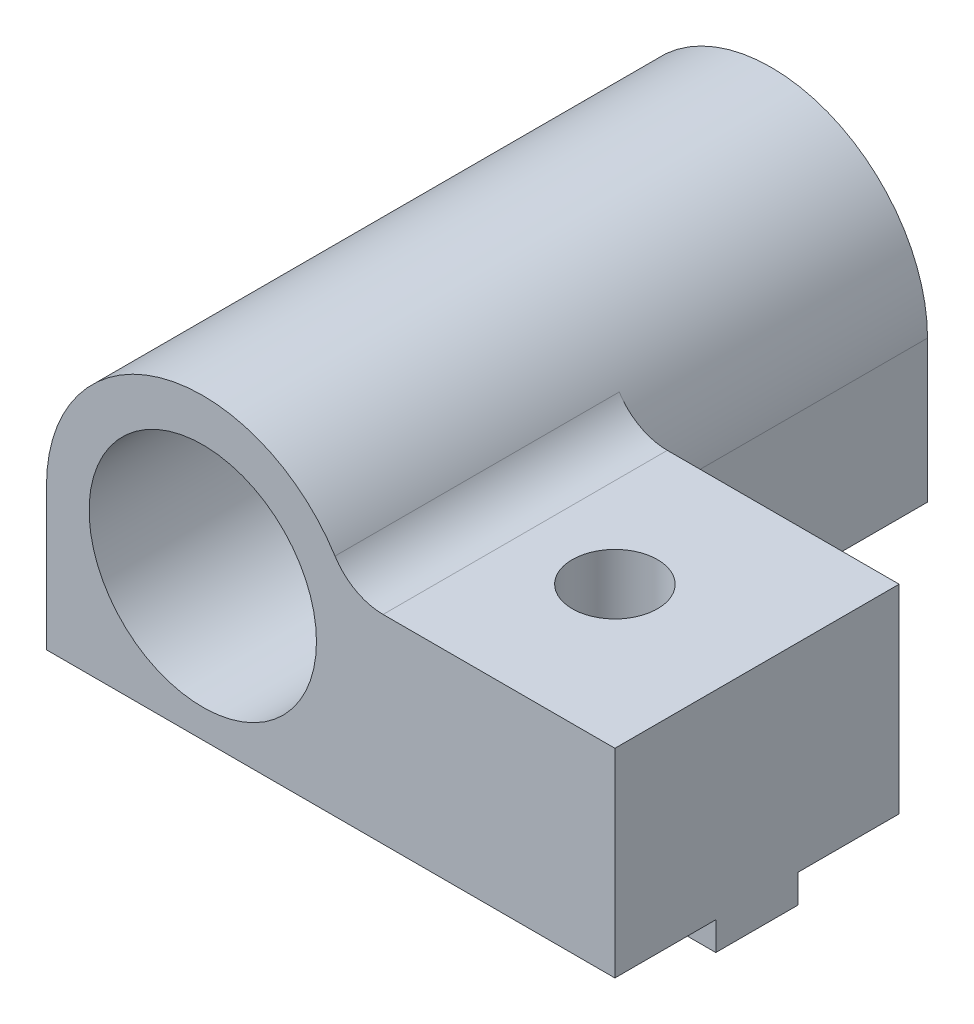
SolidWorks part; units mm, degrees
ref_plane "Front Plane" through (0, 0, 0) normal (0, 0, 1) x (1, 0, 0)
ref_plane "Top Plane" through (0, 0, 0) normal (0, 1, 0) x (1, 0, 0)
ref_plane "Right Plane" through (0, 0, 0) normal (1, 0, 0) x (0, 0, -1)
sketch "Sketch1" plane through (0, 0, 0) normal (0, 0, 1) x (1, 0, 0)
  line L0 (-5.5, 0) -> (-5.5, -5)
  line L1 (14.5, -5) -> (14.5, 2)
  line L3 (-5.5, -5) -> (14.5, -5)
  line L4 (14.5, 2) -> (5.1235, 2)
  arc A0 (-5.5, 0) -> (5.1235, 2) centre (0, 0) cw
  circle A1 centre (0, 0) radius 4
  dimension "D1" = 8
  dimension "D2" = 5.5
  dimension "D3" = 5
  dimension "D4" = 7
  dimension "D5" = 20
  dimension "D6" = 9.3765
extrude "Main" add sketch "Sketch1" along normal blind 10
sketch "Sketch3" plane through (0, -5, 0) normal (0, -1, 0) x (-1, 0, 0)
  line L0 (5.5, -10) -> (5.5, 0) construction
  line L1 (5.5, -6.45) -> (-14.5, -6.45)
  line L2 (5.5, -6.45) -> (5.5, -3.55)
  line L3 (5.5, -3.55) -> (-14.5, -3.55)
  line L4 (-14.5, -6.45) -> (-14.5, -3.55)
  line L5 (-14.5, -10) -> (-14.5, 0) construction
  line L6 (5.5, 0) -> (-14.5, 0) construction
  dimension "D1" = 2.9
  dimension "D2" = 3.55
extrude "MakerBeamRectangularGuide" add sketch "Sketch3" along normal blind 1
sketch "Sketch4" plane through (0, 2, 0) normal (0, 1, 0) x (1, 0, 0)
  line L0 (14.5, -10) -> (5.1235, -10) construction
  line L1 (14.5, -10) -> (14.5, 0) construction
  circle A0 centre (9.5, -5) radius 1.5
  dimension "D1" = 3
  dimension "D2" = 5
  dimension "D3" = 5
extrude "MakerBeamFixHole" cut sketch "Sketch4" against normal through all
fillet "Fillet1" radius 2 1 edges at (5.1235, 2, 5)
sketch "Sketch5" plane through (0, 0, 10) normal (0, 0, 1) x (1, 0, 0)
  line L0 (-5.5, -5) -> (5.5, -5)
  line L1 (-5.5, -5) -> (14.5, -5) construction
  line L2 (-5.5, -5) -> (-5.5, 0)
  line L3 (-5.5, 0) -> (-5.5, -5) construction
  line L4 (5.5, 0) -> (5.5, -5)
  arc A0 (5.5, 0) -> (-5.5, 0) centre (0, 0) ccw
  circle A1 centre (0, 0) radius 4
extrude "Boss-Extrude1" add sketch "Sketch5" along normal blind 10
ref_plane "Plane1" through (0, 0, -5) normal (0, 0, 1) x (1, 0, 0)
mirror "Mirror1" about plane through (0, 0, -5) normal (0, 0, 1) of bodies 110
sketch "Sketch6" plane through (0, 0, -5) normal (0, 0, 1) x (1, 0, 0)
  line L1 (-17.9117, -16.0858) -> (28.1433, -16.0858)
  line L2 (-17.9117, -16.0858) -> (-17.9117, 22.7052)
  line L3 (-17.9117, 22.7052) -> (28.1433, 22.7052)
  line L4 (28.1433, -16.0858) -> (28.1433, 22.7052)
extrude "Cut-Extrude1" cut sketch "Sketch6" along normal through all
